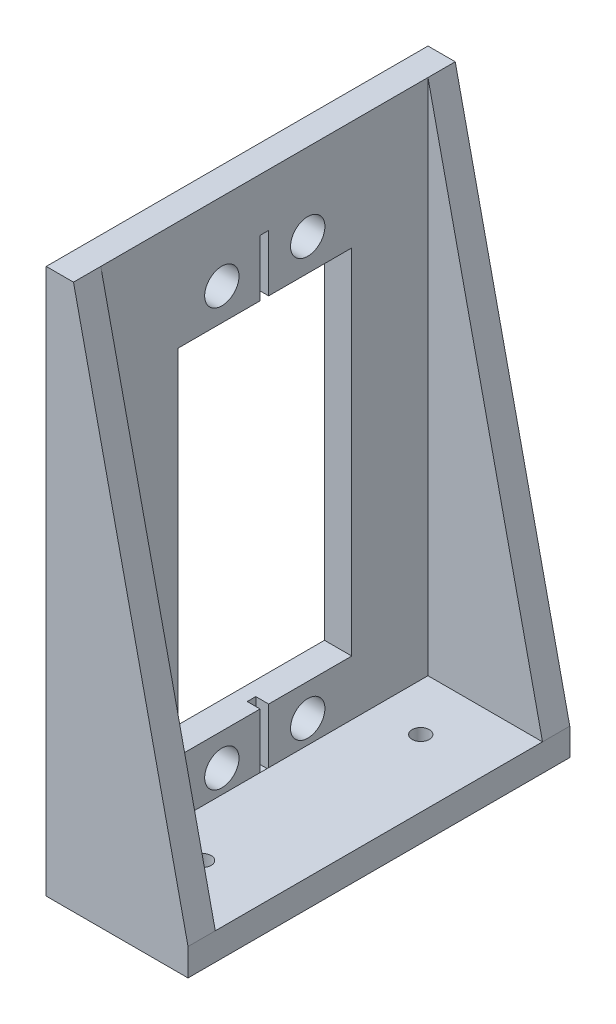
SolidWorks part; units mm, degrees
ref_plane "Front Plane" through (0, 0, 0) normal (0, 0, 1) x (1, 0, 0)
ref_plane "Top Plane" through (0, 0, 0) normal (0, 1, 0) x (1, 0, 0)
ref_plane "Right Plane" through (0, 0, 0) normal (1, 0, 0) x (0, 0, -1)
sketch "Sketch1" plane through (0, 0, 0) normal (0, 0, 1) x (1, 0, 0)
  line L0 (0, 0) -> (0, 63.5)
  line L1 (0, 63.5) -> (3.175, 63.5)
  line L2 (3.175, 63.5) -> (3.175, 3.175)
  line L3 (3.175, 3.175) -> (16.51, 3.175)
  line L4 (16.51, 3.175) -> (16.51, 0)
  line L5 (16.51, 0) -> (0, 0)
  dimension "D1" = 3.175
  dimension "D2" = 3.175
  dimension "D3" = 16.51
  dimension "D4" = 63.5
extrude "Boss-Extrude1" add sketch "Sketch1" along normal mid plane 44.45
sketch "Sketch3" plane through (0, 0, 22.225) normal (0, 0, 1) x (1, 0, 0)
  line L0 (3.175, 63.5) -> (16.51, 3.175)
  line L1 (16.51, 3.175) -> (3.175, 3.175)
  line L2 (3.175, 3.175) -> (3.175, 63.5)
extrude "Boss-Extrude2" add sketch "Sketch3" against normal blind 3.175
mirror "Mirror1" about plane through (0, 0, 0) normal (0, 0, 1) of "Boss-Extrude2"
sketch "Sketch4" plane through (0, 3.175, 0) normal (0, 1, 0) x (1, 0, 0)
  line L1 (3.175, 19.05) -> (16.51, 19.05) construction
  line L3 (3.175, 0) -> (16.51, 0) construction
  line L4 (3.175, -19.05) -> (3.175, 19.05) construction
  line L5 (16.51, -19.05) -> (16.51, 19.05) construction
  circle A0 centre (8.68, 12.7) radius 1
  circle A3 centre (8.68, -12.7) radius 1
  dimension "D1" = 2
  dimension "D2" = 6.35
  dimension "D3" = 5.505
extrude "Cut-Extrude2" cut sketch "Sketch4" against normal through all
sketch "Sketch5" plane through (3.175, 0, 0) normal (1, 0, 0) x (0, 0, -1)
  line L0 (-19.05, 63.5) -> (-19.05, 3.175) construction
  line L1 (-19.05, 3.175) -> (19.05, 3.175) construction
  circle A0 centre (-4.953, 5.875) radius 2
  circle A1 centre (5.047, 5.875) radius 2
  circle A2 centre (-4.953, 54.475) radius 2
  circle A3 centre (5.047, 54.475) radius 2
  dimension "D3" = 4
  dimension "D5" = 4
  dimension "D7" = 4
  dimension "D8" = 4
  dimension "D1" = 14.097
  dimension "D2" = 2.7
  dimension "D4" = 10
  dimension "D6" = 48.6
extrude "Cut-Extrude3" cut sketch "Sketch5" against normal through all
sketch "Sketch6" plane through (3.175, 0, 0) normal (1, 0, 0) x (0, 0, -1)
  line L0 (-10.08, 50.752) -> (10.174, 9.598) construction
  line L1 (-10.08, 50.752) -> (10.174, 50.752)
  line L2 (-10.08, 50.752) -> (-10.08, 9.598)
  line L3 (-10.08, 9.598) -> (10.174, 9.598)
  line L4 (10.174, 50.752) -> (10.174, 9.598)
  line L5 (10.174, 50.752) -> (-10.08, 9.598) construction
  line L6 (-4.953, 54.475) -> (5.047, 5.875) construction
  line L7 (-4.953, 5.875) -> (5.047, 54.475) construction
  point P12 (0.047, 30.175)
  point P13 (0.047, 30.175)
  dimension "D1" = 41.154
  dimension "D2" = 20.254
extrude "Cut-Extrude4" cut sketch "Sketch6" against normal through all
sketch "Sketch7" plane through (0, 50.752, 0) normal (0, -1, 0) x (1, 0, 0)
  line L0 (3.175, -10.174) -> (3.175, 10.08) construction
  line L1 (1.675, -0.5) -> (3.175, -0.5)
  line L2 (1.675, -0.5) -> (1.675, 0.5)
  line L3 (1.675, 0.5) -> (3.175, 0.5)
  line L4 (3.175, -0.5) -> (3.175, 0.5)
  line L5 (1.675, -0.5) -> (3.175, 0.5) construction
  line L6 (1.675, 0.5) -> (3.175, -0.5) construction
  line L7 (9.0805, 0) -> (-9.0805, 0) construction
  point P0 (2.425, 0)
  dimension "D1" = 1
  dimension "D2" = 1.5
extrude "Cut-Extrude5" cut sketch "Sketch7" against normal blind 6.604
extrude "Cut-Extrude6" cut sketch "Sketch7<2>" along normal blind 6.604 from surface starting at face at (1.5875, 9.598, -0.047)
sketch "Sketch7<2>" plane through (0, 50.752, 0) normal (0, -1, 0) x (1, 0, 0) same geometry as "Sketch7"
equation "\"D1@Sketch4\"=2mm"
equation "\"tightTol\" = 0.005in"
equation "\"normTol\"= 0.01in"
equation "\"looseTol\"= 0.02in"
equation "\"D2@Sketch5\"=2.7mm"
equation "\"D3@Sketch5\"=4mm"
equation "\"D4@Sketch5\"=10mm"
equation "\"D5@Sketch5\"=4mm"
equation "\"D6@Sketch5\"=48.6mm"
equation "\"D8@Sketch5\"=4mm"
equation "\"D1@Sketch6\" = 40.9mm + \"normTol\""
equation "\"D2@Sketch6\" = 20mm + \"normTol\""
equation "\"D1@Sketch7\"=1mm"
equation "\"D2@Sketch7\"=1.5mm"
equation "\"D7@Sketch5\"=4mm"
equation "\"D3@Sketch4\"=0.125000in+2.33mm"
